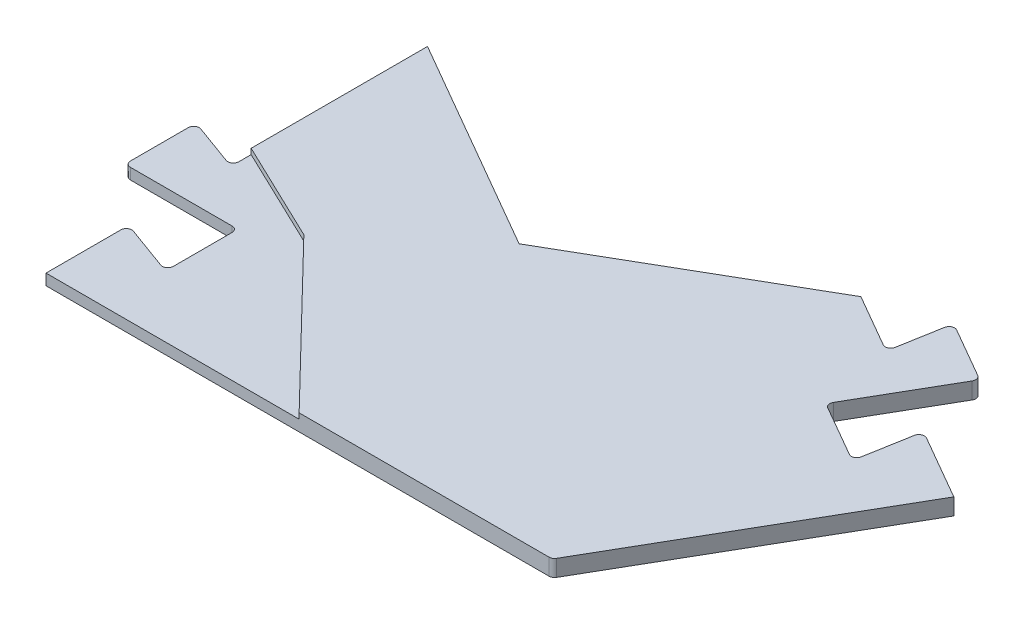
SolidWorks part; units mm, degrees
ref_plane "Přední rovina" through (0, 0, 0) normal (0, 0, 1) x (1, 0, 0)
ref_plane "Horní rovina" through (0, 0, 0) normal (0, 1, 0) x (1, 0, 0)
ref_plane "Pravá rovina" through (0, 0, 0) normal (1, 0, 0) x (0, 0, -1)
sketch "Skica1" plane through (0, 0, 0) normal (0, 1, 0) x (1, 0, 0)
  line L18 (13.6775, 53.6901) -> (26.6679, 46.1901)
  line L19 (26.6679, 46.1901) -> (0, 0)
  line L27 (-91.8562, 37.22) -> (-73.4914, 28.4198)
  line L34 (-91.8562, 0) -> (-91.8562, 15)
  line L36 (-91.8562, 15) -> (-81.3562, 11.1783)
  line L37 (-81.3562, 11.1783) -> (-81.3562, 24.2783)
  line L38 (-81.3562, 24.2783) -> (-101.8068, 24.2783)
  line L39 (-73.4914, 28.4198) -> (-45.9281, 0)
  line L44 (-91.8562, 0) -> (0, 0)
  line L45 (-91.8562, 33.5566) -> (-101.8068, 37.1783)
  line L46 (-101.8068, 37.1783) -> (-101.8068, 24.2783)
  line L47 (-91.8562, 69.22) -> (-91.8562, 33.5566)
  line L48 (-91.8562, 69.22) -> (-52.5387, 46.52)
  line L49 (-52.5387, 46.52) -> (-13.2211, 69.22)
  line L50 (13.6775, 53.6901) -> (11.7372, 42.686)
  line L51 (11.7372, 42.686) -> (0.3922, 49.236)
  line L52 (-13.2211, 69.22) -> (-2.393, 62.9684)
  line L53 (0.3922, 49.236) -> (10.6175, 66.9466)
  line L56 (-2.393, 62.9684) -> (-0.5543, 73.3966)
  line L57 (-0.5543, 73.3966) -> (10.6175, 66.9466)
  line L58 (-91.8562, 53.6901) -> (-91.8562, 1.8977) construction
  line L59 (-13.2211, 69.22) -> (26.6679, 46.1901) construction
  point P0 (0, 0)
  point P8 (-91.5815, 24.2783)
  point P23 (5.5048, 58.0913)
  dimension "D3" = 90
  dimension "D4" = 15
  dimension "D5" = 120
  dimension "D6" = 45.4
  dimension "D7" = 45.4
  dimension "D8" = 69.22
  dimension "D9" = 70
  dimension "D10" = 12.9
  dimension "D11" = 13.1
  dimension "D12" = 32
  dimension "D13" = 70
  dimension "D14" = 10.5
  dimension "D15" = 12.9
  dimension "D16" = 70
  dimension "D17" = 13.1
  dimension "D19" = 120
  dimension "D20" = 91.8562
  dimension "D21" = 10.5
  dimension "D22" = 15
  dimension "D23" = 69.22
  dimension "D24" = 120
  dimension "D25" = 20.3645
  dimension "D26" = 39.5906
extrude "Přidat vysunutím1" add sketch "Skica1" along normal blind 3 contours L57 L56 L52 L49 L48 L47 L27 L39 L44 L19 L18 L50 L51 L53 region at (-31.1142, 0, -34.1551)
extrude "Přidat vysunutím2" add sketch "Skica1<15>" along normal blind 2 contours L47 L58 L38 L37 L36 L34 L44 L39 L27 | L58 L45 L46 L38 region at (-76.8167, 0, -14.9585)
sketch "Skica1<15>" plane through (0, 0, 0) normal (0, 1, 0) x (1, 0, 0) same geometry as "Skica1"
fillet "Zaoblit1" radius 1 13 edges at (-81.3562, 1, -11.1783) (-91.8562, 1, -15) (-81.3562, 1, -24.2783) (-101.8068, 1, -24.2783) (-101.8068, 1, -37.1783) (-91.8562, 1, -33.5566) (0, 1.5, 0) (13.6775, 1.5, -53.6901) (11.7372, 1.5, -42.686) (0.3922, 1.5, -49.236) (-2.393, 1.5, -62.9684) (-0.5543, 1.5, -73.3966) (10.6175, 1.5, -66.9466)
